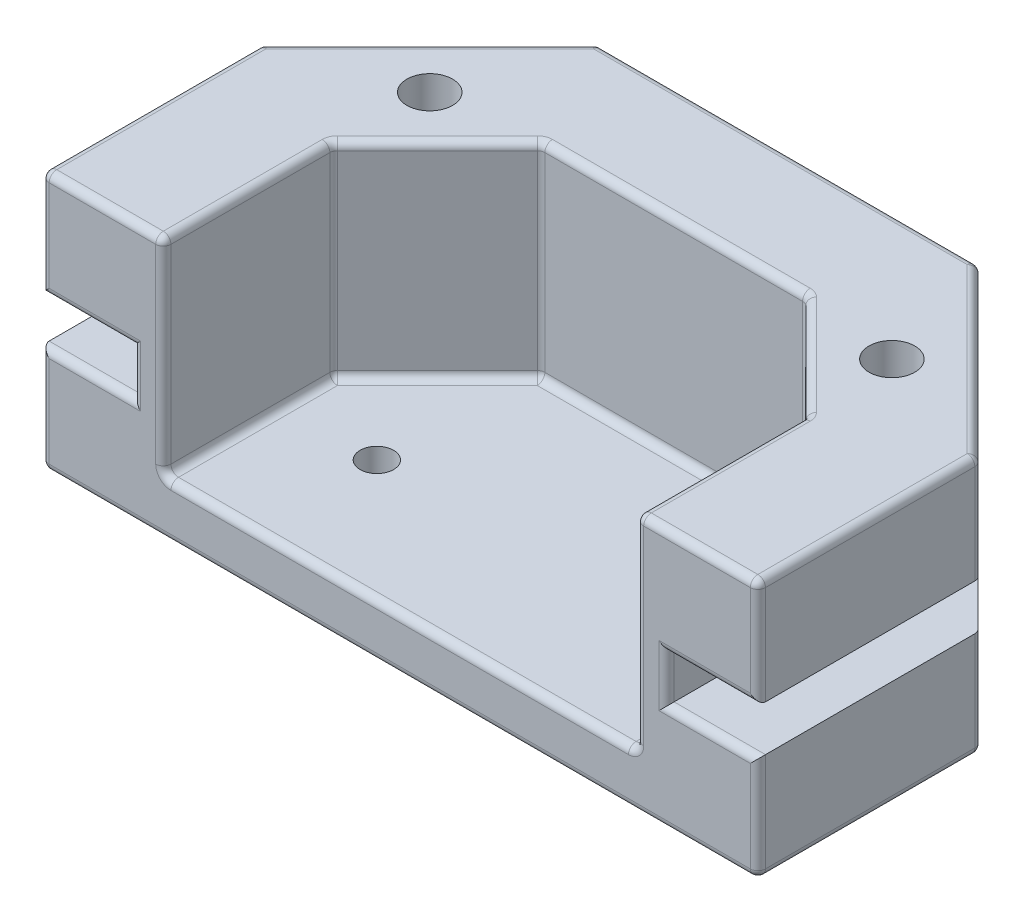
SolidWorks part; units mm, degrees
ref_plane "Front Plane" through (0, 0, 0) normal (0, 0, 1) x (1, 0, 0)
ref_plane "Top Plane" through (0, 0, 0) normal (0, 1, 0) x (1, 0, 0)
ref_plane "Right Plane" through (0, 0, 0) normal (1, 0, 0) x (0, 0, -1)
ref_plane "Motor Holder Bottom" through (0, -3.5, 0) normal (0, -1, 0) x (-1, 0, 0)
sketch "Sketch1" plane through (0, 0, 0) normal (0, 1, 0) x (1, 0, 0)
  line L5 (62.5266, -52.5) -> (68.5266, -52.5) construction
  line L6 (35, -33) -> (27.4734, -40.5266) construction
  line L7 (27.4734, -52.5) -> (21.4734, -52.5)
  line L10 (19.9734, -52.5) -> (27.4734, -52.5) construction
  line L13 (29.4734, -52.5) -> (60.5266, -52.5)
  line L16 (27.4734, -52.5) -> (27.4734, -40.5266)
  line L18 (60.5266, -52.5) -> (62.5266, -52.5)
  line L19 (55, -33) -> (62.5266, -40.5266)
  line L20 (27.4734, -40.5266) -> (35, -33)
  line L21 (62.5266, -40.5266) -> (62.5266, -52.5)
  line L22 (35, -33) -> (55, -33)
  line L23 (29.4734, -52.5) -> (29.4734, -41.3551)
  line L24 (35, -33) -> (55, -33) construction
  line L25 (29.4734, -41.3551) -> (36.3284, -34.5)
  line L26 (36.3284, -34.5) -> (53.6716, -34.5)
  line L27 (53.6716, -34.5) -> (60.5266, -41.3551)
  line L28 (60.5266, -41.3551) -> (60.5266, -52.5)
  line L29 (55, -33) -> (62.5266, -40.5266) construction
  line L30 (29.4734, -52.5) -> (27.4734, -52.5)
  line L31 (21.4734, -52.5) -> (21.4734, -38.0413)
  line L32 (21.4734, -38.0413) -> (32.5147, -27)
  line L33 (32.5147, -27) -> (57.4853, -27)
  line L34 (57.4853, -27) -> (68.5266, -38.0413)
  line L35 (68.5266, -38.0413) -> (68.5266, -52.5)
  line L36 (62.5266, -52.5) -> (68.5266, -52.5)
  dimension "D1" = 6
  dimension "D4" = 2
  dimension "D5" = 2
  dimension "D6" = 1.5
  dimension "D7" = 2
  dimension "D8" = 2
extrude "Boss-Extrude1" add sketch "Sketch1" along normal blind 10 and the other way blind 7 contours L16 | L16 L18 region at (24.4734, 0, 51.9648) region at (27.8745, 0, 46.5133)
extrude "Cut-Extrude1" cut sketch "Sketch1<3>" along normal up to surface (3 mm away) contours L16 region at (24.4734, 0, 51.9648)
sketch "Sketch1<3>" plane through (0, 0, 0) normal (0, 1, 0) x (1, 0, 0) same geometry as "Sketch1"
extrude "Boss-Extrude4" add sketch "Sketch1<5>" along normal up to surface (-3.5 mm away) from surface contours L28 L27 L26 L25 L23 L13 region at (45, 0, 44.1163) up to plane "Motor Holder Bottom" starting at face at (45, -7, 40.9827)
sketch "Sketch1<5>" plane through (0, 0, 0) normal (0, 1, 0) x (1, 0, 0) same geometry as "Sketch1"
sketch "Sketch2" plane through (0, 10, 0) normal (0, 1, 0) x (1, 0, 0)
  line L0 (26.994, -32.5207) -> (32.6509, -38.1775) construction
  line L1 (21.4734, -38.0413) -> (32.5147, -27) construction
  line L2 (29.4734, -41.3551) -> (36.3284, -34.5) construction
  line L3 (63.006, -32.5207) -> (57.3491, -38.1775) construction
  line L4 (57.4853, -27) -> (68.5266, -38.0413) construction
  line L5 (53.6716, -34.5) -> (60.5266, -41.3551) construction
  circle A0 centre (29.8225, -35.3491) radius 1.5
  circle A1 centre (60.1775, -35.3491) radius 1.5
  dimension "D1" = 3
  dimension "D2" = 3
extrude "Cut-Extrude2" cut sketch "Sketch2" against normal up to surface (17 mm away) up to face at (45, -7, 39.1804)
fillet "Fillet1" radius 0.5 48 edges at (29.4734, 10, 46.9275) (60.5266, 10, 46.9275) (60.5266, -3.5, 46.9275) (29.4734, -3.5, 46.9275) (45, -7, 52.5) (21.4734, -3.5, 52.5) (24.4734, 0, 52.5) (27.4734, 1.5, 52.5) (24.4734, 3, 52.5) (21.4734, 6.5, 52.5) (25.4734, 10, 52.5) (29.4734, 3.25, 52.5) (45, -3.5, 52.5) (60.5266, 3.25, 52.5) (64.5266, 10, 52.5) (68.5266, 6.5, 52.5) (65.5266, 3, 52.5) (62.5266, 1.5, 52.5) (65.5266, 0, 52.5) (68.5266, -3.5, 52.5) (57.0991, 10, 37.9275) (60.5266, 3.25, 41.3551) (57.0991, -3.5, 37.9275) (45, 10, 34.5) (53.6716, 3.25, 34.5) (45, -3.5, 34.5) (32.9009, 10, 37.9275) (36.3284, 3.25, 34.5) (32.9009, -3.5, 37.9275) (29.4734, 3.25, 41.3551) (21.4734, 10, 45.2707) (68.5266, 10, 45.2707) (63.006, 10, 32.5207) (45, 10, 27) (26.994, 10, 32.5207) (21.4734, 6.5, 38.0413) (32.5147, 6.5, 27) (57.4853, 6.5, 27) (68.5266, 6.5, 38.0413) (32.5147, -3.5, 27) (26.994, -7, 32.5207) (21.4734, -7, 45.2707) (21.4734, -3.5, 38.0413) (68.5266, -3.5, 38.0413) (57.4853, -3.5, 27) (45, -7, 27) (63.006, -7, 32.5207) (68.5266, -7, 45.2707)
sketch "Sketch4" plane through (0, 0, 0) normal (0, 1, 0) x (1, 0, 0)
  circle A0 centre (35.5, -44.5) radius 1.1 construction
  circle A1 centre (35.5, -44.5) radius 1.1
  circle A2 centre (54.5, -44.5) radius 1.1 construction
  circle A3 centre (54.5, -44.5) radius 1.1
extrude "Cut-Extrude3" cut sketch "Sketch4" against normal up to surface (7 mm away) from surface up to face at (45, -7, 39.2495) starting at face at (45, -3.5, 42.8541)
